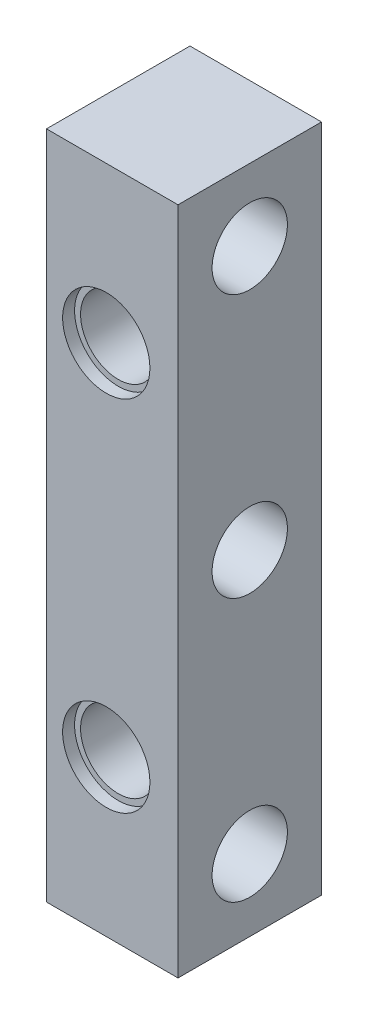
SolidWorks part; units mm, degrees
ref_plane "Front" through (0, 0, 0) normal (0, 0, 1) x (1, 0, 0)
ref_plane "Top" through (0, 0, 0) normal (0, 1, 0) x (1, 0, 0)
ref_plane "Right" through (0, 0, 0) normal (1, 0, 0) x (0, 0, -1)
sketch "Esquisse1" plane through (0, 0, 0) normal (0, 0, 1) x (1, 0, 0)
  line L1 (0, 0) -> (12, 0)
  line L2 (0, 0) -> (0, 40)
  line L3 (0, 40) -> (12, 40)
  line L4 (12, 0) -> (12, 40)
  dimension "D1" = 12
  dimension "D2" = 40
extrude "Boss.-Extru.1" add sketch "Esquisse1" along normal blind 12
sketch "Esquisse3" plane through (0, 0, 12) normal (0, 0, 1) x (1, 0, 0)
  line L0 (5, 40) -> (5, 0) construction
  line L2 (0, 0) -> (12, 0) construction
  line L3 (12, 40) -> (0, 40) construction
  line L4 (0, 40) -> (0, 0) construction
  circle A0 centre (5, 5) radius 3.15
  circle A1 centre (5, 35) radius 3.15
  dimension "D1" = 30
  dimension "D2" = 5
  dimension "D3" = 6.3
  dimension "D4" = 5
extrude "Enlèv. mat.-Extru.1" cut sketch "Esquisse3" against normal through all both and the other way through all
sketch "Esquisse4" plane through (12, 0, 0) normal (1, 0, 0) x (0, 0, -1)
  line L0 (-6, 0) -> (-6, 40) construction
  line L1 (-12, 0) -> (0, 0) construction
  line L2 (-12, 40) -> (0, 40) construction
  circle A0 centre (-6, 20) radius 3.15
  dimension "D1" = 6.3
extrude "Enlèv. mat.-Extru.2" cut sketch "Esquisse4" against normal through all both and the other way through all
sketch "Esquisse5" plane through (0, 0, 12) normal (0, 0, 1) x (1, 0, 0)
  circle A0 centre (5, 35) radius 3.65
  circle A1 centre (5, 5) radius 3.65
  dimension "D1" = 7.3
extrude "Enlèv. mat.-Extru.3" cut sketch "Esquisse5" against normal blind 1
sketch "Esquisse6" plane through (12, 0, 0) normal (1, 0, 0) x (0, 0, -1)
  circle A0 centre (-6, 20) radius 3.65
  dimension "D1" = 7.3
extrude "Enlèv. mat.-Extru.4" cut sketch "Esquisse6" against normal blind 1
sketch "Esquisse7" plane through (12, 0, 0) normal (1, 0, 0) x (0, 0, -1)
  line L1 (-12, 0) -> (-12, 40) construction
  line L2 (0, 0) -> (-12, 0)
  line L3 (0, 0) -> (0, -8)
  line L4 (0, -8) -> (-12, -8)
  line L5 (-12, 0) -> (-12, -8)
  line L6 (-12, 20) -> (0, 20) construction
  line L7 (0, 0) -> (0, 40) construction
  line L8 (-12, 40) -> (-12, 48)
  line L9 (0, 48) -> (-12, 48)
  line L10 (0, 40) -> (0, 48)
  line L11 (0, 40) -> (-12, 40)
  dimension "D1" = 8
extrude "Boss.-Extru.2" add sketch "Esquisse7" against normal up to vertex (12 mm away) up to point (0, 0, 0)
sketch "Esquisse8" plane through (0, -8, 0) normal (0, -1, 0) x (1, 0, 0)
  line L0 (0, 12) -> (12, 12) construction
  line L1 (12, 0) -> (11, 0)
  line L2 (12, 0) -> (12, 12)
  line L3 (12, 12) -> (11, 12)
  line L4 (11, 0) -> (11, 12)
  dimension "D1" = 1
extrude "Enlèv. mat.-Extru.5" cut sketch "Esquisse8" against normal through all both and the other way through all
sketch "Esquisse9" plane through (11, 0, 0) normal (1, 0, 0) x (0, 0, -1)
  line L0 (-12, 20) -> (0, 20) construction
  line L1 (-12, 48) -> (-12, -8) construction
  line L2 (0, 48) -> (0, -8) construction
  line L3 (-6, 20) -> (-6, 42) construction
  circle A0 centre (-6, 42) radius 3.15
  circle A1 centre (-6, 20) radius 3.15 construction
  circle A2 centre (-6, -2) radius 3.15
  dimension "D1" = 22
extrude "Enlèv. mat.-Extru.6" cut sketch "Esquisse9" against normal through all both and the other way through all
sketch "Esquisse10" plane through (0, 0, 0) normal (-1, 0, 0) x (0, 0, 1)
  circle A0 centre (6, 42) radius 3.65
  circle A1 centre (6, -2) radius 3.65
  circle A2 centre (6, 20) radius 3.65
  dimension "D1" = 7.3
extrude "Enlèv. mat.-Extru.7" cut sketch "Esquisse10" against normal blind 1
